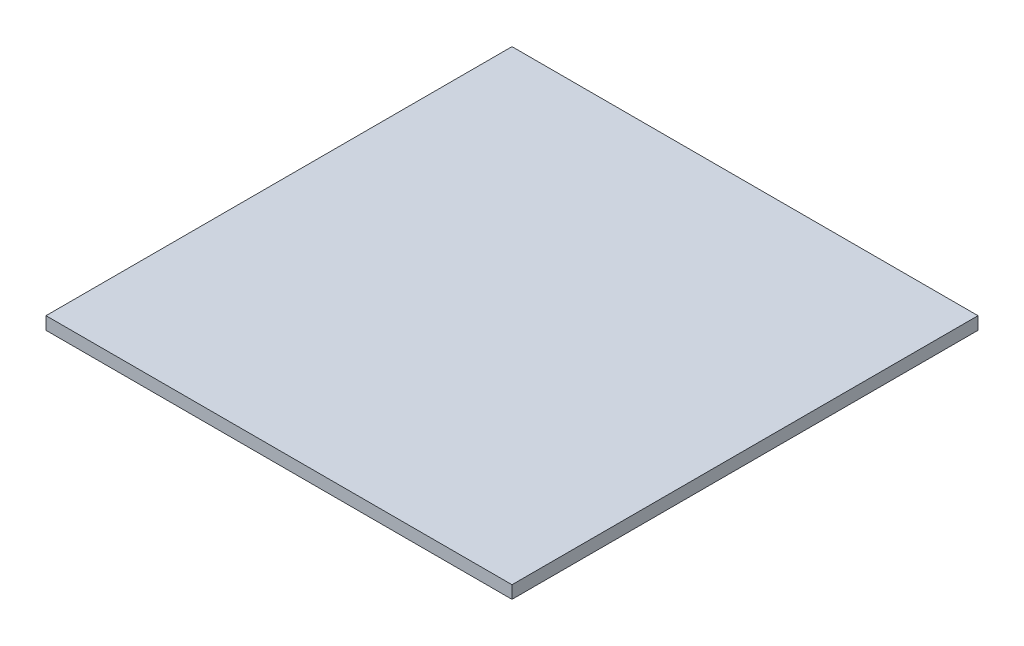
SolidWorks part; units mm, degrees
material "Acrylic (Medium-high impact)"
ref_plane "Front Plane" through (0, 0, 0) normal (0, 0, 1) x (1, 0, 0)
ref_plane "Top Plane" through (0, 0, 0) normal (0, 1, 0) x (1, 0, 0)
ref_plane "Right Plane" through (0, 0, 0) normal (1, 0, 0) x (0, 0, -1)
sketch "Sketch2" plane through (0, 0, 0) normal (0, 1, 0) x (1, 0, 0)
  line L11 (-714.2229, -7.6601) -> (-494.2229, -7.6601)
  line L12 (-714.2229, -7.6601) -> (-714.2229, 212.3399)
  line L13 (-714.2229, 212.3399) -> (-494.2229, 212.3399)
  line L14 (-494.2229, -7.6601) -> (-494.2229, 212.3399)
  dimension "D1" = 220
  dimension "D2" = 220
extrude "Boss-Extrude1" add sketch "Sketch2" along normal blind 6
